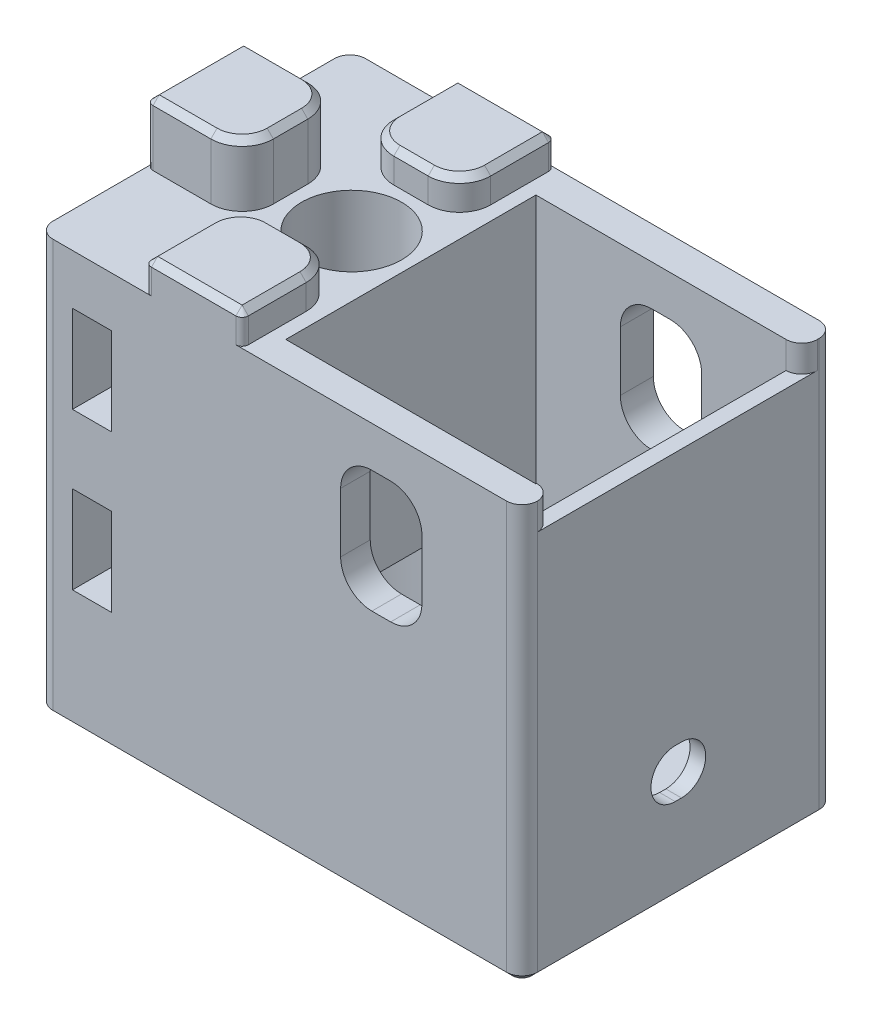
SolidWorks part; units mm, degrees
ref_plane "前视基准面" through (0, 0, 0) normal (0, 0, 1) x (1, 0, 0)
ref_plane "上视基准面" through (0, 0, 0) normal (0, 1, 0) x (1, 0, 0)
ref_plane "右视基准面" through (0, 0, 0) normal (1, 0, 0) x (0, 0, -1)
sketch "草图1" plane through (0, 0, 0) normal (0, 0, 1) x (1, 0, 0)
  line L1 (-15.5, 13.25) -> (15.5, 13.25)
  line L2 (-15.5, 13.25) -> (-15.5, -13.25)
  line L3 (-15.5, -13.25) -> (15.5, -13.25)
  line L4 (15.5, 13.25) -> (15.5, -13.25)
  line L5 (-15.5, 13.25) -> (15.5, -13.25) construction
  line L6 (-15.5, -13.25) -> (15.5, 13.25) construction
  point P0 (0, 0)
  dimension "D1" = 26.5
  dimension "D2" = 31
extrude "凸台-拉伸1" add sketch "草图1" along normal blind 20 contours L1 L4 L3 L2
sketch "草图3" plane through (0, 13.25, 0) normal (0, 1, 0) x (1, 0, 0)
  line L1 (-1.5, -2.1082) -> (14.5, -2.1082)
  line L2 (-1.5, -2.1082) -> (-1.5, -18.1082)
  line L3 (-1.5, -18.1082) -> (14.5, -18.1082)
  line L4 (14.5, -2.1082) -> (14.5, -18.1082)
  line L5 (-1.5, -2.1082) -> (14.5, -18.1082) construction
  line L6 (-1.5, -18.1082) -> (14.5, -2.1082) construction
  line L7 (15.5, -20) -> (15.5, 0) construction
  point P0 (6.5, -10.1082)
  dimension "D1" = 16
  dimension "D2" = 16
  dimension "D3" = 9
extrude "切除-拉伸1" cut sketch "草图3" against normal blind 23.5 contours L1 L4 L3 L2
sketch "草图4" plane through (0, 13.25, 0) normal (0, 1, 0) x (1, 0, 0)
  line L1 (-15.5, -6.8) -> (-9.4, -6.8)
  line L2 (-15.5, -6.8) -> (-15.5, -13)
  line L3 (-15.5, -13) -> (-9.4, -13)
  line L4 (-9.4, -6.8) -> (-9.4, -13)
  line L5 (-15.5, -6.8) -> (-9.4, -13) construction
  line L6 (-15.5, -13) -> (-9.4, -6.8) construction
  line L7 (-15.5, -20) -> (15.5, -20) construction
  line L8 (-15.5, -20) -> (-15.5, 0) construction
  point P0 (-12.45, -9.9)
  dimension "D1" = 6.1
  dimension "D2" = 6.2
  dimension "D3" = 7
  dimension "D4" = 0
extrude "凸台-拉伸2" add sketch "草图4" along normal blind 4
sketch "草图5" plane through (0, 13.25, 0) normal (0, 1, 0) x (1, 0, 0)
  line L0 (-15.5, 0) -> (15.5, 0) construction
  line L1 (-8.6, 0) -> (-2.4, 0)
  line L2 (-8.6, 0) -> (-8.6, -6.1)
  line L3 (-8.6, -6.1) -> (-2.4, -6.1)
  line L4 (-2.4, 0) -> (-2.4, -6.1)
  line L5 (-8.6, 0) -> (-2.4, -6.1) construction
  line L6 (-8.6, -6.1) -> (-2.4, 0) construction
  line L7 (-8.6, -13.9) -> (-2.4, -13.9)
  line L8 (-8.6, -13.9) -> (-8.6, -20)
  line L9 (-8.6, -20) -> (-2.4, -20)
  line L10 (-2.4, -13.9) -> (-2.4, -20)
  line L11 (-8.6, -13.9) -> (-2.4, -20) construction
  line L12 (-8.6, -20) -> (-2.4, -13.9) construction
  line L13 (-15.5, -20) -> (15.5, -20) construction
  line L14 (-15.5, -6.8) -> (-15.5, 0) construction
  line L15 (-15.5, -20) -> (-15.5, -13) construction
  point P0 (-5.5, -3.05)
  point P5 (-5.5, -16.95)
  dimension "D1" = 0
  dimension "D2" = 0
  dimension "D3" = 6.2
  dimension "D4" = 6.2
  dimension "D5" = 6.9
  dimension "D6" = 6.9
  dimension "D7" = 6.1
  dimension "D8" = 6.1
extrude "凸台-拉伸3" add sketch "草图5" along normal blind 2
sketch "草图6" plane through (0, 13.25, 0) normal (0, 1, 0) x (1, 0, 0)
  line L0 (-2.4, -6.1) -> (-2.4, 0) construction
  line L1 (-15.5, 0) -> (-8.6, 0) construction
  circle A0 centre (-5.4, -10) radius 3.2
  dimension "D2" = 6.4
  dimension "D1" = 3
  dimension "D3" = 10
extrude "切除-拉伸2" cut sketch "草图6" against normal through all
sketch "草图8" plane through (0, 0, 20) normal (0, 0, 1) x (1, 0, 0)
  line L1 (5.9, 10.65) -> (7.1, 10.65)
  line L2 (3.9, 8.65) -> (3.9, 4.85)
  line L3 (5.9, 2.85) -> (7.1, 2.85)
  line L4 (9.1, 8.65) -> (9.1, 4.85)
  line L5 (3.9, 10.65) -> (9.1, 2.85) construction
  line L6 (3.9, 2.85) -> (9.1, 10.65) construction
  line L7 (15.5, 13.25) -> (15.5, -13.25) construction
  line L8 (-2.4, 13.25) -> (15.5, 13.25) construction
  arc A0 (3.9, 8.65) -> (5.9, 10.65) centre (5.9, 8.65) cw
  arc A1 (9.1, 8.65) -> (7.1, 10.65) centre (7.1, 8.65) ccw
  arc A2 (7.1, 2.85) -> (9.1, 4.85) centre (7.1, 4.85) ccw
  arc A3 (5.9, 2.85) -> (3.9, 4.85) centre (5.9, 4.85) cw
  point P0 (6.5, 6.75)
  dimension "D4" = 2
  dimension "D5" = 2
  dimension "D6" = 2
  dimension "D7" = 2
  dimension "D1" = 5.2
  dimension "D2" = 7.8
  dimension "D3" = 6.5
  dimension "D8" = 9
extrude "切除-拉伸3" cut sketch "草图8" against normal through all
sketch "草图9" plane through (0, 0, 20) normal (0, 0, 1) x (1, 0, 0)
  line L1 (-13.25, 10.05) -> (-10.75, 10.05)
  line L2 (-13.25, 10.05) -> (-13.25, 4.45)
  line L3 (-13.25, 4.45) -> (-10.75, 4.45)
  line L4 (-10.75, 10.05) -> (-10.75, 4.45)
  line L5 (-13.25, 10.05) -> (-10.75, 4.45) construction
  line L6 (-13.25, 4.45) -> (-10.75, 10.05) construction
  line L7 (-13.25, 0.05) -> (-10.75, 0.05)
  line L8 (-13.25, 0.05) -> (-13.25, -5.55)
  line L9 (-13.25, -5.55) -> (-10.75, -5.55)
  line L10 (-10.75, 0.05) -> (-10.75, -5.55)
  line L11 (-13.25, 0.05) -> (-10.75, -5.55) construction
  line L12 (-13.25, -5.55) -> (-10.75, 0.05) construction
  line L13 (-15.5, 13.25) -> (-8.6, 13.25) construction
  line L14 (-15.5, 13.25) -> (-15.5, -13.25) construction
  point P0 (-12, 7.25)
  point P5 (-12, -2.75)
  dimension "D1" = 5.6
  dimension "D2" = 5.6
  dimension "D3" = 2.5
  dimension "D4" = 2.5
  dimension "D5" = 10
  dimension "D6" = 6
  dimension "D7" = 3.5
extrude "切除-拉伸4" cut sketch "草图9" against normal blind 8.3
sketch "草图10" plane through (0, 13.25, 0) normal (0, 1, 0) x (1, 0, 0)
  line L0 (15.5, -20) -> (15.5, 0) construction
  line L1 (14.5, -2.1082) -> (15.5, -2.1082)
  line L2 (14.5, -2.1082) -> (14.5, -18.0611)
  line L3 (14.5, -18.0611) -> (15.5, -18.0611)
  line L4 (15.5, -2.1082) -> (15.5, -18.0611)
  line L5 (14.5, -2.1082) -> (15.5, -18.0611) construction
  line L6 (14.5, -18.0611) -> (15.5, -2.1082) construction
  point P4 (15, -10.0847)
extrude "切除-拉伸5" cut sketch "草图10" against normal blind 1.72
sketch "草图11" plane through (0, -13.25, 0) normal (0, -1, 0) x (1, 0, 0)
  line L0 (-15.5, 20) -> (15.5, 20) construction
  line L1 (-15.5, 20) -> (-15.5, 0) construction
  circle A0 centre (-5.5, 10) radius 5.5
  dimension "D1" = 10
  dimension "D3" = 11
  dimension "D2" = 10
extrude "切除-拉伸6" cut sketch "草图11" against normal blind 11 contours A0
sketch "草图12" plane through (0, -13.25, 0) normal (0, -1, 0) x (-1, 0, 0)
  line L0 (15.5, -20) -> (-15.5, -20) construction
  line L2 (-15.5, -20) -> (-15.5, 0) construction
  circle A0 centre (-7.5, -10) radius 2.05
  dimension "D1" = 10
  dimension "D3" = 4.1
  dimension "D2" = 8
extrude "切除-拉伸7" cut sketch "草图12" against normal through all
sketch "草图13" plane through (15.5, 0, 0) normal (1, 0, 0) x (0, 0, -1)
  line L0 (-10.2, -6.25) -> (-9.8, -6.25) construction
  line L1 (-10.2, -4.7) -> (-9.8, -4.7)
  line L2 (-10.2, -7.8) -> (-9.8, -7.8)
  line L3 (-20, -13.25) -> (0, -13.25) construction
  line L4 (-20, 13.25) -> (-20, -13.25) construction
  arc A0 (-10.2, -4.7) -> (-10.2, -7.8) centre (-10.2, -6.25) ccw
  arc A1 (-9.8, -7.8) -> (-9.8, -4.7) centre (-9.8, -6.25) ccw
  point P2 (-10, -6.25)
  point P7 (-10, -7.8)
  point P8 (-11.75, -6.25)
  point P9 (-8.25, -6.25)
  dimension "D1" = 3.1
  dimension "D2" = 3.5
  dimension "D3" = 7
  dimension "D4" = 10
extrude "切除-拉伸8" cut sketch "草图13" against normal up to next
fillet "圆角2" radius 1 4 edges at (-15.5, 0, 20) (-15.5, 0, 0) (15.5, 0, 20) (15.5, 0, 0)
fillet "圆角3" radius 1 2 edges at (15.5, 12.39, 18.0611) (15.5, 12.39, 2.1082)
sketch "草图14" plane through (-15.5, 0, 0) normal (-1, 0, 0) x (0, 0, 1)
  line L1 (19, 13.25) -> (13, 13.25) construction
  line L2 (20, 13.25) -> (20, -13.25) construction
  circle A0 centre (5, 7.25) radius 1.6
  circle A1 centre (15, 7.25) radius 1.6
  circle A2 centre (5, -2.75) radius 1.6
  circle A3 centre (15, -2.75) radius 1.6
  dimension "D1" = 3.2
  dimension "D2" = 10
  dimension "D3" = 5
  dimension "D4" = 10
  dimension "D5" = 6
extrude "切除-拉伸9" cut sketch "草图14" against normal up to surface (2.25 mm away) up to face at (-13.25, 7.25, 15.85)
ref_plane "基准面1" through (0, 0, 10) normal (0, 0, -1) x (-1, 0, 0)
mirror "镜向1" about plane through (0, 0, 10) normal (0, 0, -1) of "切除-拉伸4"
chamfer "倒角2" distance 0.4 angle 45 8 edges at (15.5, -13.25, 10) (15.2071, -13.25, 19.7071) (15.2071, -13.25, 0.2929) (0, -13.25, 20) (0, -13.25, 0) (-15.2071, -13.25, 19.7071) (-15.2071, -13.25, 0.2929) (-15.5, -13.25, 10)
sketch "草图15" plane through (0, -2.25, 0) normal (0, -1, 0) x (1, 0, 0)
  line L0 (-8.6, 14.5431) -> (-8.6, 5.4569)
  line L1 (-2.2, 14.4) -> (-2.2, 5.6)
  line L4 (-9.9733, 13.2) -> (-1.5, 13.2)
  line L5 (-1.5, 6.2251) -> (-1.5, 13.7749)
  line L6 (-1.5, 6.2251) -> (-1.5, 13.7749)
  line L7 (-9.9733, 6.8) -> (-1.5, 6.8)
  circle A6 centre (-5.4, 10) radius 3.2 construction
  arc A7 (-1.5, 13.7749) -> (-1.5, 6.2251) centre (-5.5, 10) ccw
  arc A8 (-1.5, 13.7749) -> (-1.5, 6.2251) centre (-5.5, 10) ccw
  line M7 (-1.5, 6.2251) -> (-1.5, 13.7749)
  arc M8 (-1.5, 13.7749) -> (-1.5, 6.2251) centre (-5.5, 10) ccw
  dimension "D1" = 0
  dimension "D2" = 0
extrude "凸台-拉伸4" add sketch "草图15" along normal blind 0.2 contours L4 L0 M8 | L0 L4 L1 M8 | L1 L4 M7 M8 | L7 L0 M8 | L7 L0 L1 M8 | L7 L1 M8 M7 region at (-5.4355, -2.25, 14.2087) region at (-9.0843, -2.25, 13.6738) region at (-1.8902, -2.25, 13.6706) region at (-5.4355, -2.25, 5.7913) region at (-9.0843, -2.25, 6.3262) region at (-1.8902, -2.25, 6.3294)
extrude "凸台-拉伸5" add sketch "草图15<4>" along normal blind 0.4 contours L4 L0 M8 | L7 L0 L4 M8 | L7 L0 M8 | L1 L4 M7 M8 | L1 L7 L6 L4 | L7 L1 M8 M7 region at (-9.0843, -2.25, 13.6738) region at (-9.6577, -2.25, 10) region at (-1.8902, -2.25, 13.6706) region at (-9.0843, -2.25, 6.3262) region at (-1.85, -2.25, 10) region at (-1.8902, -2.25, 6.3294)
sketch "草图15<4>" plane through (0, -2.25, 0) normal (0, -1, 0) x (1, 0, 0) same geometry as "草图15"
fillet "圆角4" radius 2 6 edges at (-8.6, 14.25, 13.9) (-2.4, 14.25, 13.9) (-9.4, 15.25, 13) (-9.4, 15.25, 6.8) (-2.4, 14.25, 6.1) (-8.6, 14.25, 6.1)
fillet "圆角5" radius 0.4 6 edges at (-8.6, 14.25, 20) (-2.4, 14.25, 20) (-2.4, 14.25, 0) (-15.5, 15.25, 13) (-15.5, 15.25, 6.8) (-8.6, 14.25, 0)
chamfer "倒角3" distance 0.4 angle 45 24 edges at (-8.0142, 15.25, 14.4858) (-5.5, 15.25, 13.9) (-2.9858, 15.25, 14.4858) (-2.4, 15.25, 17.75) (-2.5172, 15.25, 19.8828) (-5.5, 15.25, 20) (-8.4828, 15.25, 19.8828) (-8.6, 15.25, 17.75) (-15.3828, 17.25, 6.9172) (-13.25, 17.25, 6.8) (-9.9858, 17.25, 7.3858) (-9.4, 17.25, 9.9) (-9.9858, 17.25, 12.4142) (-13.25, 17.25, 13) (-15.3828, 17.25, 12.8828) (-15.5, 17.25, 9.9) (-2.9858, 15.25, 5.5142) (-5.5, 15.25, 6.1) (-8.0142, 15.25, 5.5142) (-8.6, 15.25, 2.25) (-8.4828, 15.25, 0.1172) (-5.5, 15.25, 0) (-2.5172, 15.25, 0.1172) (-2.4, 15.25, 2.25)
chamfer "倒角4" distance 0.4 angle 45 1 edges at (-5.5, -13.25, 4.5)
chamfer "倒角5" distance 1 angle 45 1 edges at (7.5, -13.25, 7.95)
